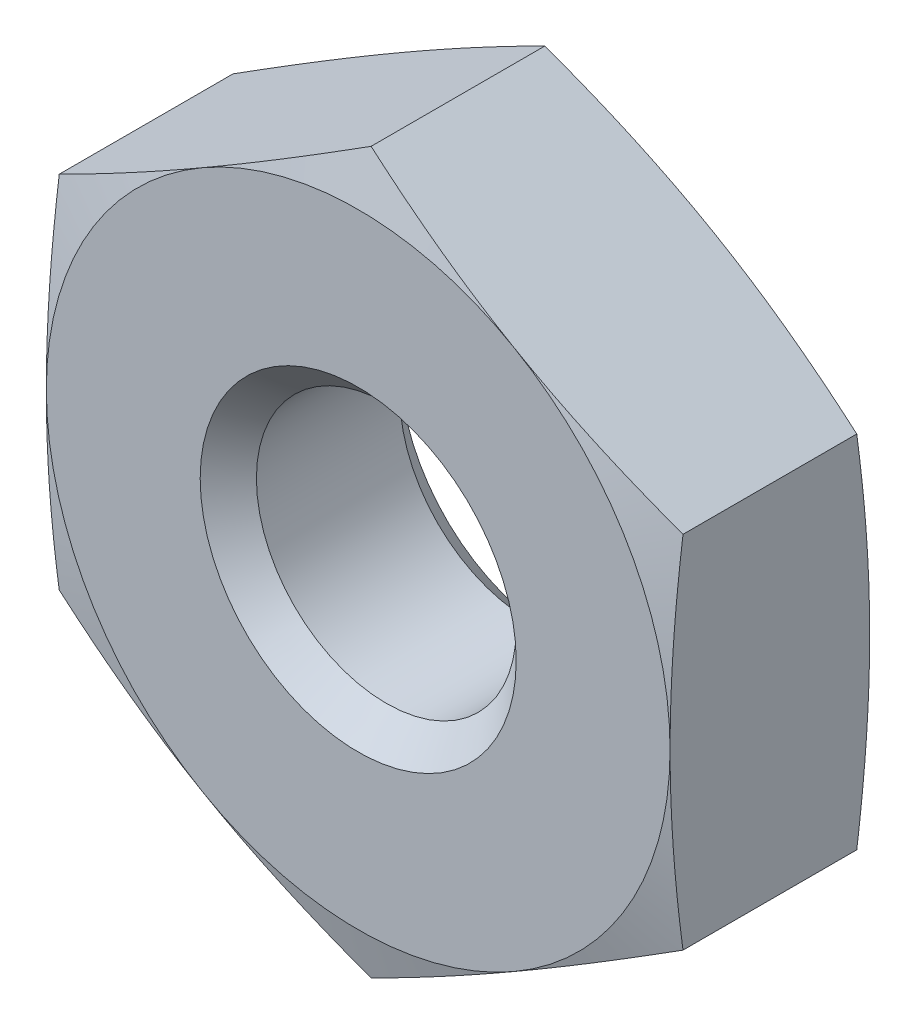
SolidWorks part; units mm, degrees
material "AISI 304"
ref_plane "Front Plane" through (0, 0, 0) normal (0, 0, 1) x (1, 0, 0)
ref_plane "Top Plane" through (0, 0, 0) normal (0, 1, 0) x (1, 0, 0)
ref_plane "Right Plane" through (0, 0, 0) normal (1, 0, 0) x (0, 0, -1)
sketch "Sketch1" plane through (0, 0, 0) normal (1, 0, 0) x (0, 0, -1)
  line L0 (0, 0) -> (0, 4.7625)
  line L1 (0, 4.7625) -> (0.2552, 5.715)
  line L2 (0.2552, 5.715) -> (2.7928, 5.715)
  line L3 (2.7928, 5.715) -> (3.048, 4.7625)
  line L4 (3.048, 4.7625) -> (3.048, 0)
  line L5 (3.048, 0) -> (0, 0)
  line L6 (3.048, 0) -> (0, 0) construction
sketch "Sketch2" plane through (0, 0, 0) normal (0, 0, 1) x (1, 0, 0)
  line L0 (-9.525, 9.525) -> (-9.525, -9.525)
  line L1 (-9.525, -9.525) -> (9.525, -9.525)
  line L2 (9.525, -9.525) -> (9.525, 9.525)
  line L3 (9.525, 9.525) -> (-9.525, 9.525)
  line L4 (-4.7625, 2.7496) -> (-4.7625, -2.7496)
  line L5 (-4.7625, -2.7496) -> (0, -5.4993)
  line L6 (0, -5.4993) -> (4.7625, -2.7496)
  line L7 (4.7625, -2.7496) -> (4.7625, 2.7496)
  line L8 (4.7625, 2.7496) -> (0, 5.4993)
  line L9 (0, 5.4993) -> (-4.7625, 2.7496)
revolve "Revolve1" add sketch "Sketch1" angle 360 about L6 reverse direction yes
extrude "Cut-Extrude1" cut sketch "Sketch2" against normal blind 3.048
sketch "Sketch3" plane through (0, 0, 0) normal (1, 0, 0) x (0, 0, -1)
  line L0 (0, 0) -> (0, 2.413)
  line L1 (0, 2.413) -> (0.4293, 1.9837)
  line L2 (0.4293, 1.9837) -> (2.6187, 1.9837)
  line L3 (2.6187, 1.9837) -> (3.048, 2.413)
  line L4 (3.048, 2.413) -> (3.048, 0)
  line L5 (3.048, 0) -> (0, 0)
  line L6 (3.048, 0) -> (0, 0) construction
revolve "Cut-Revolve1" cut sketch "Sketch3" angle 360 about L6 reverse direction yes
cosmetic thread "Cosmetic Thread1" parameters "D1"=3.048, "D2"=4.826
ref_plane "NUT XY" through (0, 0, 0) normal (0, 0, 1) x (1, 0, 0)
ref_plane "NUT XZ" through (0, 0, 0) normal (0, -1, 0) x (-1, 0, 0)
ref_plane "NUT YZ" through (0, 0, 0) normal (1, 0, 0) x (0, 0, -1)
ref_axis "NUT X" through (-80.9, 0, 0) along (1, 0, 0)
ref_axis "NUT Y" through (0, -50, 0) along (0, 1, 0)
ref_axis "NUT Z" through (0, 0, 80.9) along (0, 0, -1)
sketch3d "NUT"
  point P0 (0, 0, 0)
ref_plane "a1 XY" through (0, 0, 0) normal (0, 0, 1) x (1, 0, 0)
ref_plane "a1 XZ" through (0, 4.7625, 0) normal (0, -1, 0) x (-1, 0, 0)
ref_plane "a1 YZ" through (-4.7625, 0, 0) normal (1, 0, 0) x (0, 0, -1)
ref_axis "a1 X" through (-80.9, 4.7625, 0) along (1, 0, 0)
ref_axis "a1 Y" through (-4.7625, -50, 0) along (0, 1, 0)
ref_axis "a1 Z" through (-4.7625, 4.7625, 80.9) along (0, 0, -1)
sketch3d "a1"
  point P0 (-4.7625, 4.7625, 0)
ref_plane "a2 XY" through (0, 0, 0) normal (0, 0, 1) x (1, 0, 0)
ref_plane "a2 XZ" through (0, 4.7625, 0) normal (0, -1, 0) x (-1, 0, 0)
ref_plane "a2 YZ" through (4.7625, 0, 0) normal (1, 0, 0) x (0, 0, -1)
ref_axis "a2 X" through (-80.9, 4.7625, 0) along (1, 0, 0)
ref_axis "a2 Y" through (4.7625, -50, 0) along (0, 1, 0)
ref_axis "a2 Z" through (4.7625, 4.7625, 80.9) along (0, 0, -1)
sketch3d "a2"
  point P0 (4.7625, 4.7625, 0)
ref_plane "b1 XY" through (0, 0, 0) normal (1, 0, 0) x (0, 0, -1)
ref_plane "b1 XZ" through (0, 4.7625, 0) normal (0, -1, 0) x (-1, 0, 0)
ref_plane "b1 YZ" through (0, 0, 0) normal (0, 0, -1) x (-1, 0, 0)
ref_axis "b1 X" through (0, 4.7625, 80.9) along (0, 0, -1)
ref_axis "b1 Y" through (0, -50, 0) along (0, 1, 0)
ref_axis "b1 Z" through (80.9, 4.7625, 0) along (-1, 0, 0)
sketch3d "b1"
  point P0 (0, 4.7625, 0)
ref_plane "b2 XY" through (0, 0, 0) normal (1, 0, 0) x (0, 0, -1)
ref_plane "b2 XZ" through (0, 4.7625, 0) normal (0, -1, 0) x (-1, 0, 0)
ref_plane "b2 YZ" through (0, 0, -3.048) normal (0, 0, -1) x (-1, 0, 0)
ref_axis "b2 X" through (0, 4.7625, 80.9) along (0, 0, -1)
ref_axis "b2 Y" through (0, -50, -3.048) along (0, 1, 0)
ref_axis "b2 Z" through (80.9, 4.7625, -3.048) along (-1, 0, 0)
sketch3d "b2"
  point P0 (0, 4.7625, -3.048)
ref_plane "e XY" through (0, 0, 0) normal (1, 0, 0) x (0, 0, -1)
ref_plane "e XZ" through (0, 0, 0) normal (0, -1, 0) x (-1, 0, 0)
ref_plane "e YZ" through (0, 0, -3.048) normal (0, 0, -1) x (-1, 0, 0)
ref_axis "e X" through (0, 0, 80.9) along (0, 0, -1)
ref_axis "e Y" through (0, -50, -3.048) along (0, 1, 0)
ref_axis "e Z" through (80.9, 0, -3.048) along (-1, 0, 0)
sketch3d "e"
  point P0 (0, 0, -3.048)
ref_plane "ol1 XY" through (0, 0, 0) normal (0, 1, 0) x (1, 0, 0)
ref_plane "ol1 XZ" through (0, 0, -4.7625) normal (0, 0, 1) x (1, 0, 0)
ref_plane "ol1 YZ" through (0, 0, 0) normal (1, 0, 0) x (0, 0, -1)
ref_axis "ol1 X" through (-80.9, 0, -4.7625) along (1, 0, 0)
ref_axis "ol1 Y" through (0, 0, 50) along (0, 0, -1)
ref_axis "ol1 Z" through (0, 50, -4.7625) along (0, -1, 0)
sketch3d "ol1"
  point P0 (0, 0, -4.7625)
ref_plane "ol2 XY" through (0, 0, 0) normal (0, 1, 0) x (1, 0, 0)
ref_plane "ol2 XZ" through (0, 0, -4.7625) normal (0, 0, 1) x (1, 0, 0)
ref_plane "ol2 YZ" through (3.048, 0, 0) normal (1, 0, 0) x (0, 0, -1)
ref_axis "ol2 X" through (-80.9, 0, -4.7625) along (1, 0, 0)
ref_axis "ol2 Y" through (3.048, 0, 50) along (0, 0, -1)
ref_axis "ol2 Z" through (3.048, 50, -4.7625) along (0, -1, 0)
sketch3d "ol2"
  point P0 (3.048, 0, -4.7625)
ref_plane "th1 XY" through (0, 0, 0) normal (1, 0, 0) x (0, 0, -1)
ref_plane "th1 XZ" through (0, 2.413, 0) normal (0, -1, 0) x (-1, 0, 0)
ref_plane "th1 YZ" through (0, 0, -3.048) normal (0, 0, -1) x (-1, 0, 0)
ref_axis "th1 X" through (0, 2.413, 80.9) along (0, 0, -1)
ref_axis "th1 Y" through (0, -50, -3.048) along (0, 1, 0)
ref_axis "th1 Z" through (80.9, 2.413, -3.048) along (-1, 0, 0)
sketch3d "th1"
  point P0 (0, 2.413, -3.048)
ref_plane "th2 XY" through (0, 0, 0) normal (1, 0, 0) x (0, 0, -1)
ref_plane "th2 XZ" through (0, -2.413, 0) normal (0, -1, 0) x (-1, 0, 0)
ref_plane "th2 YZ" through (0, 0, -3.048) normal (0, 0, -1) x (-1, 0, 0)
ref_axis "th2 X" through (0, -2.413, 80.9) along (0, 0, -1)
ref_axis "th2 Y" through (0, -50, -3.048) along (0, 1, 0)
ref_axis "th2 Z" through (80.9, -2.413, -3.048) along (-1, 0, 0)
sketch3d "th2"
  point P0 (0, -2.413, -3.048)
